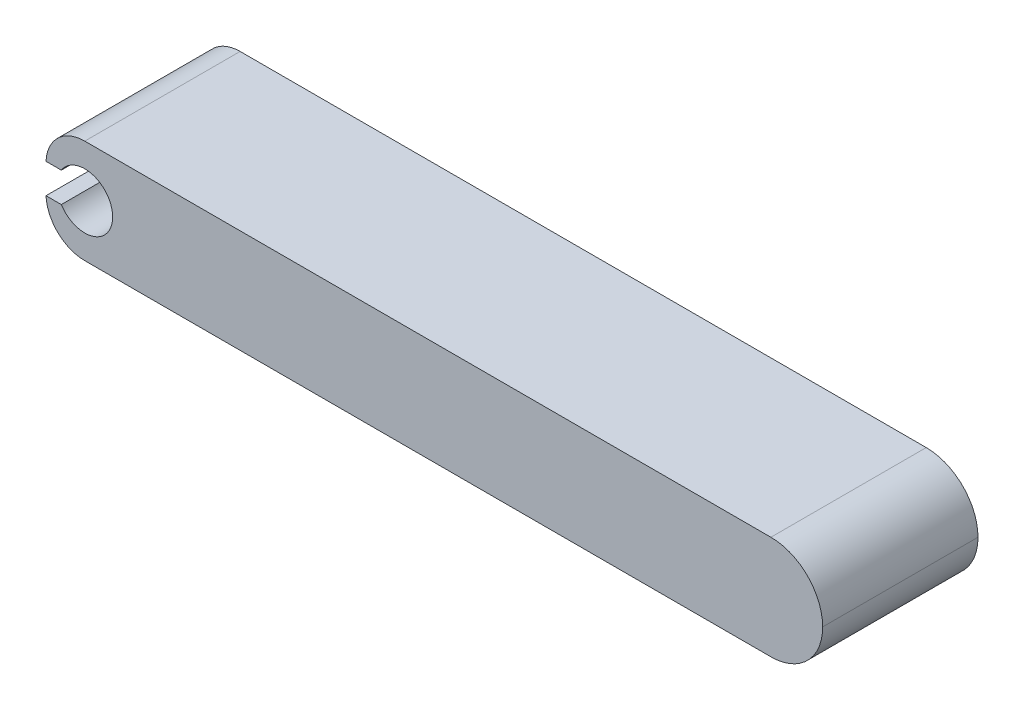
SolidWorks part; units mm, degrees
ref_plane "Plan de face" through (0, 0, 0) normal (0, 0, 1) x (1, 0, 0)
ref_plane "Plan de dessus" through (0, 0, 0) normal (0, 1, 0) x (1, 0, 0)
ref_plane "Plan de droite" through (0, 0, 0) normal (1, 0, 0) x (0, 0, -1)
sketch "Esquisse1" plane through (0, 0, 0) normal (0, 0, 1) x (1, 0, 0)
  line L1 (0, 0) -> (60, 0)
  line L2 (0, 0) -> (0, 8)
  line L3 (0, 8) -> (60, 8)
  line L4 (60, 0) -> (60, 8)
  dimension "D1" = 8
  dimension "D2" = 60
extrude "Boss.-Extru.1" add sketch "Esquisse1" along normal blind 12
sketch "Esquisse2" plane through (0, 0, 12) normal (0, 0, 1) x (1, 0, 0)
  line L0 (0, 4) -> (3, 4) construction
  line L1 (0, 8) -> (0, 0) construction
  circle A0 centre (3, 4) radius 2.15
  dimension "D1" = 4.3
  dimension "D2" = 3
extrude "Enlèv. mat.-Extru.1" cut sketch "Esquisse2" against normal through all both and the other way through all
sketch "Esquisse3" plane through (0, 0, 12) normal (0, 0, 1) x (1, 0, 0)
  line L0 (0, 4) -> (3.0244, 4) construction
  line L1 (0, 8) -> (0, 0) construction
  line L2 (0, 5.15) -> (2, 5.15)
  line L3 (2, 5.15) -> (2, 2.85)
  line L4 (0, 5.15) -> (0, 2.85)
  line L5 (0, 2.85) -> (2, 2.85)
  point P8 (2, 4)
  dimension "D1" = 2.3
  dimension "D2" = 2
extrude "Enlèv. mat.-Extru.2" cut sketch "Esquisse3" against normal through all both and the other way through all
fillet "Congé1" radius 4 2 edges at (60, 0, 6) (60, 8, 6)
fillet "Congé2" radius 3 2 edges at (0, 0, 6) (0, 8, 6)
